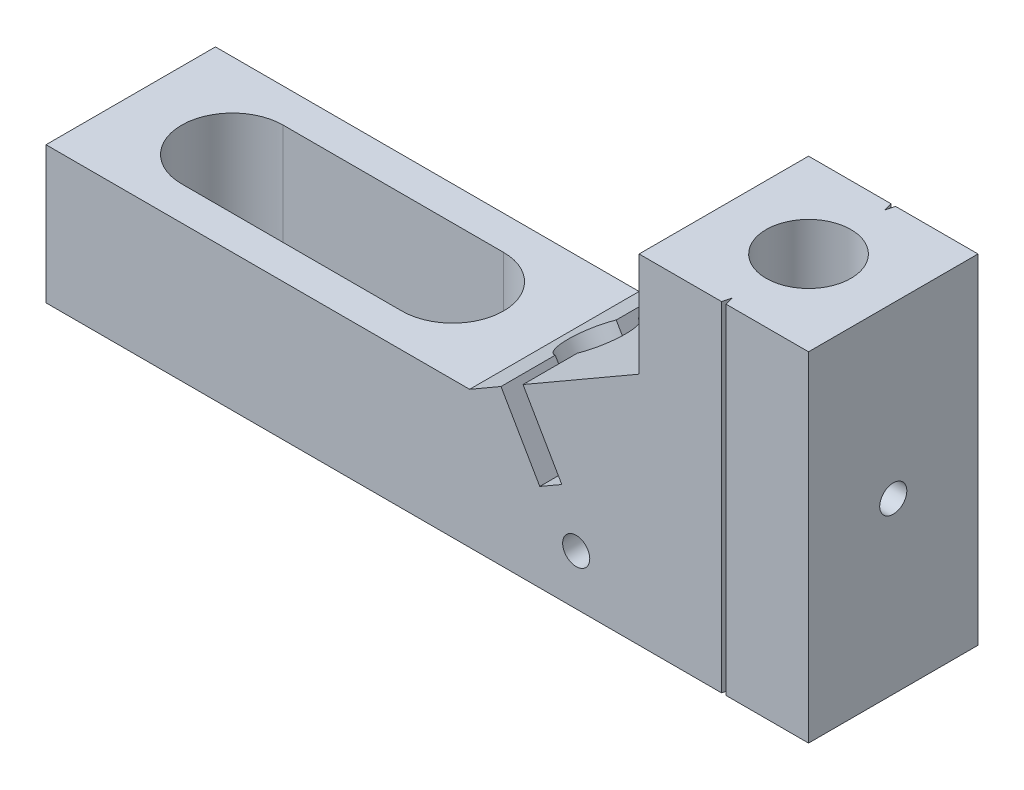
SolidWorks part; units mm, degrees
ref_plane "Front Plane" through (0, 0, 0) normal (0, 0, 1) x (1, 0, 0)
ref_plane "Top Plane" through (0, 0, 0) normal (0, 1, 0) x (1, 0, 0)
ref_plane "Right Plane" through (0, 0, 0) normal (1, 0, 0) x (0, 0, -1)
sketch "Sketch1" plane through (0, 0, 0) normal (0, 1, 0) x (1, 0, 0)
  line L1 (-13.6389, 9.0278) -> (6.3611, 9.0278)
  line L2 (-13.6389, 9.0278) -> (-13.6389, -0.9722)
  line L3 (-13.6389, -0.9722) -> (6.3611, -0.9722)
  line L4 (6.3611, 9.0278) -> (6.3611, -0.9722)
  dimension "D1" = 20
  dimension "D2" = 10
extrude "Boss-Extrude1" add sketch "Sketch1" along normal blind 20
sketch "Sketch2" plane through (0, 20, 0) normal (0, 1, 0) x (1, 0, 0)
  line L0 (-13.6389, 4.0278) -> (6.3611, 4.0278) construction
  line L1 (-13.6389, 9.0278) -> (-13.6389, -0.9722) construction
  line L2 (6.3611, -0.9722) -> (6.3611, 9.0278) construction
  line L3 (1.4951, -0.9722) -> (1.3611, -0.4722)
  line L4 (-13.6389, -0.9722) -> (6.3611, -0.9722) construction
  line L5 (1.3611, -0.4722) -> (1.2271, -0.9722)
  line L6 (1.4951, -0.9722) -> (1.2271, -0.9722)
  line L7 (1.3611, 8.5278) -> (1.2271, 9.0278)
  line L8 (1.4951, 9.0278) -> (1.3611, 8.5278)
  line L9 (1.4951, 9.0278) -> (1.2271, 9.0278)
  circle A0 centre (1.3611, 4.0278) radius 2.5
  dimension "D1" = 5
  dimension "D2" = 5
  dimension "D3" = 30
  dimension "D4" = 0.5
extrude "Cut-Extrude1" cut sketch "Sketch2" against normal through all
sketch "Sketch3" plane through (0, 0, 0.9722) normal (0, 0, 1) x (1, 0, 0)
  line L0 (-13.6389, 20) -> (-3.6389, 20)
  line L1 (-13.6389, 20) -> (1.2271, 20) construction
  line L2 (-3.6389, 13.8564) -> (-10.4894, 9.9013)
  line L3 (-13.6389, 20) -> (-13.6389, 0) construction
  line L4 (-13.6389, 8.0829) -> (-13.6389, 20)
  line L5 (-3.6389, 13.8564) -> (-3.6389, 20)
  line L6 (-13.6389, 0) -> (1.2271, 0) construction
  line L7 (-11.1389, 9.5263) -> (-5.6389, 0) construction
  line L8 (6.3611, 20) -> (6.3611, 0) construction
  line L10 (-10.4894, 9.9013) -> (-8.2009, 5.9375)
  line L11 (-11.7884, 9.1513) -> (-9.4999, 5.1875)
  line L12 (-8.2009, 5.9375) -> (-9.4999, 5.1875)
  line L13 (-11.7884, 9.1513) -> (-13.6389, 8.0829)
  point P1 (-8.8504, 5.5625)
  point P17 (-8.3889, 4.7631)
  dimension "D1" = 30
  dimension "D2" = 11
  dimension "D3" = 12
  dimension "D4" = 10
  dimension "D5" = 1.5
  dimension "D6" = 4.577
extrude "Cut-Extrude2" cut sketch "Sketch3" against normal through all
sketch "Sketch5" plane through (-6.9097, 11.968, 0) normal (-0.5, 0.866, 0) x (0.866, 0.5, 0)
  line L0 (-4.1334, 9.0278) -> (-4.1334, -0.9722) construction
  line L1 (-4.1334, 4.0278) -> (-5.6334, 4.0278) construction
  line L2 (-5.6334, 9.0278) -> (-5.6334, -0.9722) construction
  circle A0 centre (-4.8834, 4.0278) radius 1.95
  point P5 (-4.1334, 4.0278)
  dimension "D1" = 3.9
extrude "Cut-Extrude5" cut sketch "Sketch5" against normal through all
sketch "Sketch6" plane through (6.3611, 0, 0) normal (1, 0, 0) x (0, 0, -1)
  line L0 (9.0278, 20) -> (9.0278, 0) construction
  line L1 (-0.9722, 20) -> (9.0278, 20) construction
  point P0 (4.0278, 10)
  point P4 (9.0278, 10)
  point P8 (4.0278, 20)
hole_wizard "M2x0.4 Tapped Hole1" positions "Sketch7" profile "Sketch8" tap size "M2x0.4" standard "BSI"
sketch "Sketch7" plane through (6.3611, 0, 0) normal (1, 0, 0) x (0, 0, -1)
  point P0 (4.0278, 10)
sketch "Sketch8" plane through (6.3611, 10, -4.0278) normal (0, 1, 0) x (0, 0, -1)
  line L0 (0, 0) -> (0, 6.4807)
  line L1 (0, 6.4807) -> (0.8, 6)
  line L2 (0.8, 6) -> (0.8, 0)
  line L5 (0.8, 0) -> (0, 0)
  line L10 (0, 6.4807) -> (-0.8, 6) construction
  line L11 (0, -6.35) -> (0, 107.95) construction
  dimension "Tap Drill Dia." = 1.6
  dimension "Tap Drill Depth" = 6
  dimension "Drill Angle" = 118
cosmetic thread "Hole Thread1" parameters "D1"=4, "D2"=2
hole_wizard "M2x0.4 Tapped Hole2" positions "Sketch9" profile "Sketch10" tap size "M2x0.4" standard "BSI"
sketch "Sketch9" plane through (0, 0, 0.9722) normal (0, 0, 1) x (1, 0, 0)
  line L0 (-9.4999, 5.1875) -> (-8.2009, 5.9375) construction
  line L1 (-7.3504, 2.9644) -> (-8.8504, 5.5625) construction
  point P0 (-7.3504, 2.9644)
  dimension "D1" = 3
sketch "Sketch10" plane through (-7.3504, 2.9644, 0.9722) normal (1, 0, 0) x (0, -1, 0)
  line L0 (0, 0) -> (0, 6.4807)
  line L1 (0, 6.4807) -> (0.8, 6)
  line L2 (0.8, 6) -> (0.8, 0)
  line L5 (0.8, 0) -> (0, 0)
  line L10 (0, 6.4807) -> (-0.8, 6) construction
  line L11 (0, -6.35) -> (0, 107.95) construction
  dimension "Tap Drill Dia." = 1.6
  dimension "Tap Drill Depth" = 6
  dimension "Drill Angle" = 118
cosmetic thread "Hole Thread2" parameters "D1"=4, "D2"=2
sketch "Sketch14" plane through (-13.6389, 0, 0) normal (-1, 0, 0) x (0, 0, 1)
  line L4 (0.9722, 0) -> (0.9722, 8.0829)
  line L5 (0.9722, 8.0829) -> (-9.0278, 8.0829)
  line L6 (-9.0278, 8.0829) -> (-9.0278, 0)
  line L7 (-9.0278, 0) -> (0.9722, 0)
  line L8 (0.9722, 0) -> (0.9722, 8.0829)
  line L9 (0.9722, 8.0829) -> (-9.0278, 8.0829)
  line L10 (-9.0278, 8.0829) -> (-9.0278, 0)
  line L11 (-9.0278, 0) -> (0.9722, 0)
  dimension "D1" = 0
extrude "Boss-Extrude3" add sketch "Sketch14" along normal blind 25
sketch "Sketch15" plane through (0, 8.0829, 0) normal (0, 1, 0) x (1, 0, 0)
  line L0 (-13.6389, 9.0278) -> (-13.6389, -0.9722) construction
  line L1 (-38.6389, -0.9722) -> (-38.6389, 9.0278) construction
  line L2 (-32.6389, 4.0278) -> (-19.6389, 4.0278) construction
  line L3 (-38.6389, -0.9722) -> (-13.6389, -0.9722) construction
  line L4 (-19.6389, 1.0278) -> (-32.6389, 1.0278)
  line L5 (-32.6389, 7.0278) -> (-19.6389, 7.0278)
  line L6 (-38.6389, 9.0278) -> (-13.6389, 9.0278) construction
  arc A0 (-19.6389, 1.0278) -> (-19.6389, 7.0278) centre (-19.6389, 4.0278) ccw
  arc A1 (-32.6389, 7.0278) -> (-32.6389, 1.0278) centre (-32.6389, 4.0278) ccw
  point P2 (-26.1389, 4.0278)
  point P5 (-13.6389, 4.0278)
  point P11 (-38.6389, 4.0278)
  point P13 (-26.1389, -0.9722)
  dimension "D1" = 6
  dimension "D2" = 6
  dimension "D3" = 13
extrude "Cut-Extrude7" cut sketch "Sketch15" against normal up to next
